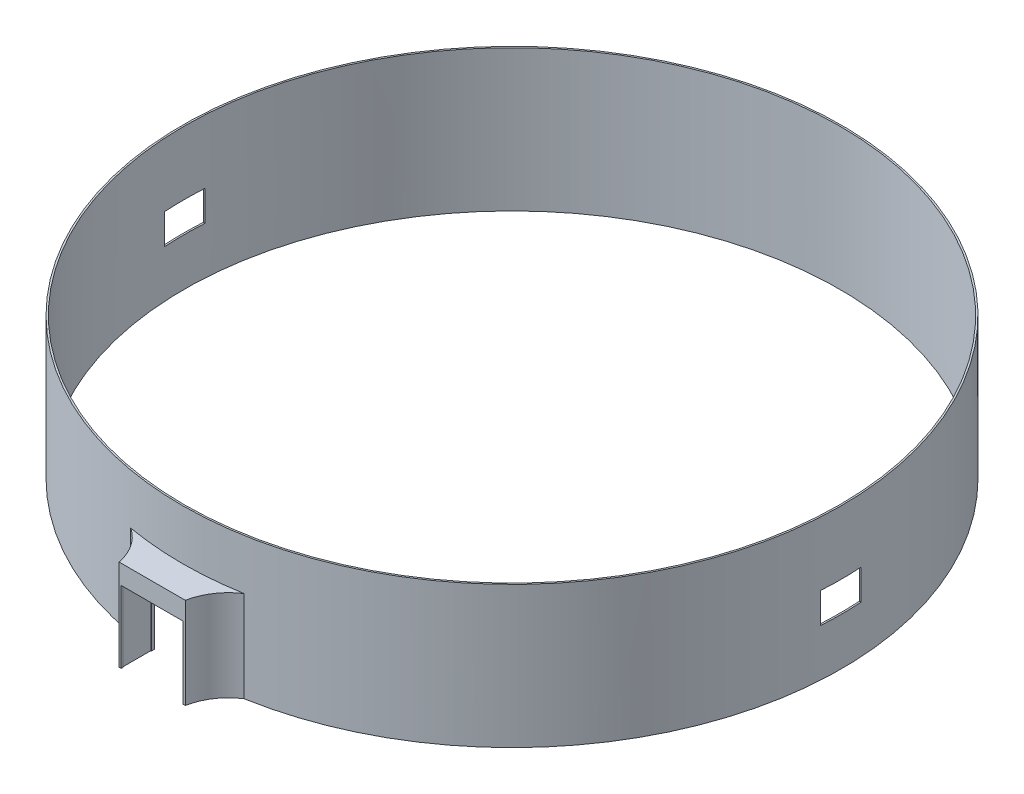
SolidWorks part; units mm, degrees
ref_plane "Front Plane" through (0, 0, 0) normal (0, 0, 1) x (1, 0, 0)
ref_plane "Top Plane" through (0, 0, 0) normal (0, 1, 0) x (1, 0, 0)
ref_plane "Right Plane" through (0, 0, 0) normal (1, 0, 0) x (0, 0, -1)
sketch "Sketch1" plane through (0, 0, 0) normal (0, 1, 0) x (1, 0, 0)
  circle A0 centre (0, 0) radius 9945.7494
  circle A1 centre (0, 0) radius 9850
extrude "Boss-Extrude1" add sketch "Sketch1" along normal blind 4267.2 contours A0
sketch "Sketch2" plane through (0, 4267.2, 0) normal (0, 1, 0) x (1, 0, 0)
  circle A0 centre (0, 0) radius 9895.7494
  circle A1 centre (0, 0) radius 9945.7494 construction
  dimension "D1" = 50
extrude "Cut-Extrude1" cut sketch "Sketch2" against normal blind 4267.2 contours A0
ref_plane "Plane2" through (0, 0, 9945.7494) normal (0, 0, 1) x (1, 0, 0)
sketch "Sketch4" plane through (0, 0, 9945.7494) normal (0, 0, 1) x (1, 0, 0)
  line L0 (0, -2346.96) -> (0, 2346.96) construction
  line L1 (1000, 0) -> (-1000, 0)
  line L2 (1000, 0) -> (1000, 2750)
  line L3 (1000, 2750) -> (-1000, 2750)
  line L4 (-1000, 0) -> (-1000, 2750)
  line L5 (1000, 0) -> (-1000, 2750) construction
  line L6 (1000, 2750) -> (-1000, 0) construction
  line L7 (10940.3244, 0) -> (-10940.3244, 0) construction
  point P0 (0, 1375)
  dimension "D1" = 2750
  dimension "D2" = 2000
extrude "Boss-Extrude2" add sketch "Sketch4" along normal blind 914.4 separate body
sketch "Sketch5" plane through (0, 0, 10860.1494) normal (0, 0, 1) x (1, 0, 0)
  line L0 (0, -2346.96) -> (0, 2346.96) construction
  line L1 (935, 0) -> (-935, 0)
  line L2 (935, 0) -> (935, 2170)
  line L3 (935, 2170) -> (-935, 2170)
  line L4 (-935, 0) -> (-935, 2170)
  line L5 (935, 0) -> (-935, 2170) construction
  line L6 (935, 2170) -> (-935, 0) construction
  line L7 (-1000, 0) -> (1000, 0) construction
  point P0 (0, 1085)
  dimension "D1" = 1870
  dimension "D2" = 2170
extrude "Cut-Extrude2" cut sketch "Sketch5" against normal mid plane 5000
sketch "Sketch6" plane through (-935, 0, 0) normal (1, 0, 0) x (0, 0, -1)
  line L0 (-10860.1494, 2170) -> (-10860.1494, 0) construction
  line L1 (-9945.7494, -75.4869) -> (-10810.1494, -75.4869)
  line L2 (-9945.7494, -75.4869) -> (-9945.7494, 2147.3115)
  line L3 (-9945.7494, 2147.3115) -> (-10810.1494, 2147.3115)
  line L4 (-10810.1494, -75.4869) -> (-10810.1494, 2147.3115)
  line L5 (-9945.7494, -75.4869) -> (-10810.1494, 2147.3115) construction
  line L6 (-9945.7494, 2147.3115) -> (-10810.1494, -75.4869) construction
  line L7 (-9945.7494, 2346.96) -> (-9945.7494, -2346.96) construction
  point P0 (-10377.9494, 1035.9123)
  dimension "D1" = 50
extrude "Cut-Extrude3" cut sketch "Sketch6" against normal blind 16.77
mirror "Mirror1" about plane through (0, 0, 0) normal (1, 0, 0) of "Cut-Extrude3"
sketch "Sketch7" plane through (0, 2170, 0) normal (0, -1, 0) x (1, 0, 0)
  line L0 (0, -2346.96) -> (0, 2346.96) construction
  line L1 (943.385, 10041.4502) -> (-943.385, 10041.4502)
  line L2 (943.385, 10041.4502) -> (943.385, 10810.1494)
  line L3 (943.385, 10810.1494) -> (-943.385, 10810.1494)
  line L4 (-943.385, 10041.4502) -> (-943.385, 10810.1494)
  line L5 (943.385, 10041.4502) -> (-943.385, 10810.1494) construction
  line L6 (943.385, 10810.1494) -> (-943.385, 10041.4502) construction
  line L7 (-951.77, 10810.1494) -> (-935, 10810.1494) construction
  line L8 (935, 10860.1494) -> (-935, 10860.1494) construction
  point P0 (0, 10425.7998)
  dimension "D1" = 50
extrude "Cut-Extrude4" cut sketch "Sketch7" against normal blind 16.77
sketch "Sketch8" plane through (0, 0, 0) normal (0, 1, 0) x (1, 0, 0)
  line L1 (-2346.96, -9945.7494) -> (2346.96, -9945.7494) construction
  line L2 (-1000, -10860.1494) -> (-1000, -9945.7494) construction
  line L3 (-1000, -9945.7494) -> (-1000, -10860.1494)
  line L4 (0, -2346.96) -> (0, 2346.96) construction
  line L5 (1000, -9945.7494) -> (1000, -10860.1494)
  line L6 (-1000, -9895.349) -> (1000, -9895.349)
  line L7 (1000, -9945.7494) -> (-1000, -9945.7494)
  circle A0 centre (0, 0) radius 9945.7494 construction
  arc A1 (-1000, -10860.1494) -> (-1709.7578, -9797.6865) centre (-2617.2235, -11172.2028) ccw
  arc A2 (-1709.7578, -9797.6865) -> (-1000, -9895.349) centre (0, 0) ccw
  arc A3 (1000, -10860.1494) -> (1709.7578, -9797.6865) centre (2617.2235, -11172.2028) cw
  arc A4 (1709.7578, -9797.6865) -> (1000, -9895.349) centre (0, 0) cw
extrude "Boss-Extrude3" add sketch "Sketch8" along normal up to surface (2750 mm away) up to face at (0, 2750, 10402.9494)
sketch "Sketch9" plane through (0, 0, 9945.7494) normal (0, 0, 1) x (1, 0, 0)
  line L1 (926.615, -141.7417) -> (-935, -141.7417)
  line L2 (926.615, -141.7417) -> (926.615, 2170)
  line L3 (926.615, 2170) -> (-935, 2170)
  line L4 (-935, -141.7417) -> (-935, 2170)
  line L5 (926.615, -141.7417) -> (-935, 2170) construction
  line L6 (926.615, 2170) -> (-935, -141.7417) construction
  point P0 (-4.1925, 1014.1291)
extrude "Cut-Extrude5" cut sketch "Sketch9" against normal blind 4000
sketch "Sketch10" plane through (0, 0, 0) normal (1, 0, 0) x (0, 0, -1)
  line L0 (0, 2424.9179) -> (0, -2424.9179) construction
  line L1 (609.6, 1430.1679) -> (-609.6, 1430.1679)
  line L2 (609.6, 1430.1679) -> (609.6, 2344.5679)
  line L3 (609.6, 2344.5679) -> (-609.6, 2344.5679)
  line L4 (-609.6, 1430.1679) -> (-609.6, 2344.5679)
  line L5 (609.6, 1430.1679) -> (-609.6, 2344.5679) construction
  line L6 (609.6, 2344.5679) -> (-609.6, 1430.1679) construction
  point P0 (0, 1887.3679)
  dimension "D1" = 914.4
  dimension "D2" = 90
  dimension "D3" = 1219.2
extrude "Cut-Extrude6" cut sketch "Sketch10" against normal through all both and the other way through all
